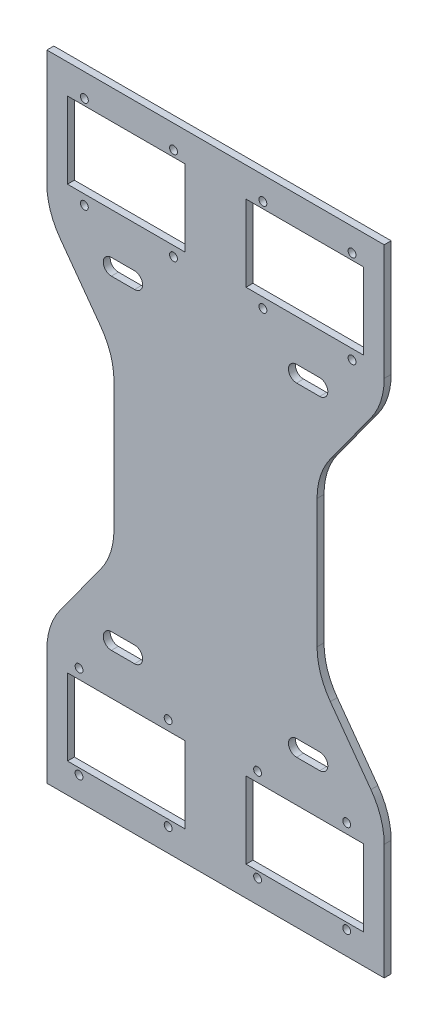
SolidWorks part; units mm, degrees
ref_plane "Alzado" through (0, 0, 0) normal (0, 0, 1) x (1, 0, 0)
ref_plane "Planta" through (0, 0, 0) normal (0, 1, 0) x (1, 0, 0)
ref_plane "Vista lateral" through (0, 0, 0) normal (1, 0, 0) x (0, 0, -1)
sketch "Croquis1" plane through (0, 0, 0) normal (0, 0, 1) x (1, 0, 0)
  line L1 (72.8628, -137.1535) -> (-72.8628, -137.1535)
  line L2 (72.8628, -137.1535) -> (72.8628, -77.4151)
  line L3 (72.8628, 137.1535) -> (-72.8628, 137.1535)
  line L4 (-72.8628, -137.1535) -> (-72.8628, -77.4151)
  line L5 (72.8628, -137.1535) -> (-72.8628, 137.1535) construction
  line L6 (72.8628, 137.1535) -> (-72.8628, -137.1535) construction
  line L7 (-72.8628, 0) -> (72.8628, 0) construction
  line L8 (0, -137.1535) -> (0, 137.1535) construction
  line L9 (-43.8628, -37.5) -> (-43.8628, 37.5)
  line L10 (-43.8628, 37.5) -> (-72.8628, 77.4151)
  line L11 (-43.8628, -37.5) -> (-72.8628, -77.4151)
  line L12 (43.8628, -37.5) -> (72.8628, -77.4151)
  line L13 (43.8628, -37.5) -> (43.8628, 37.5)
  line L14 (43.8628, 37.5) -> (72.8628, 77.4151)
  line L15 (-72.8628, 77.4151) -> (-72.8628, 137.1535)
  line L16 (72.8628, 77.4151) -> (72.8628, 137.1535)
  point P0 (0, 0)
  point P11 (0, 0)
  point P14 (-43.8628, 0)
  dimension "D1" = 145.7256
  dimension "D2" = 274.3069
  dimension "D3" = 144
  dimension "D4" = 144
  dimension "D5" = 29
  dimension "D6" = 75
  dimension "D7" = 137.1535
extrude "Saliente-Extruir1" add sketch "Croquis1" along normal blind 3
fillet "Redondeo1" radius 30 8 edges at (72.8628, 77.4151, 1.5) (43.8628, 37.5, 1.5) (43.8628, -37.5, 1.5) (72.8628, -77.4151, 1.5) (-43.8628, -37.5, 1.5) (-72.8628, -77.4151, 1.5) (-43.8628, 37.5, 1.5) (-72.8628, 77.4151, 1.5)
sketch "mid bores" plane through (0, 0, 0) normal (0, 0, 1) x (1, 0, 0)
  point P0 (-58, 71)
  point P1 (0, 110)
  point P2 (58, 71)
  point P4 (0, -110)
  point P5 (58, -71)
  point P6 (0, 0)
  point P7 (-58, -71)
  dimension "D1" = 71
  dimension "D2" = 110
  dimension "D3" = 58
  dimension "D6" = 110
  dimension "D4" = 2
  dimension "D5" = 2
sketch "Croquis2" plane through (0, 0, 3) normal (0, 0, 1) x (1, 0, 0)
  line L0 (-45, 70) -> (-35, 70) construction
  line L1 (-45, 73.5) -> (-35, 73.5)
  line L2 (-45, 66.5) -> (-35, 66.5)
  arc A0 (-45, 73.5) -> (-45, 66.5) centre (-45, 70) ccw
  arc A1 (-35, 66.5) -> (-35, 73.5) centre (-35, 70) ccw
  point P2 (-40, 70)
  point P10 (0, 0)
  dimension "D1" = 7
  dimension "D2" = 10
  dimension "D3" = 40
  dimension "D4" = 70
extrude "Cortar-Extruir1" cut sketch "Croquis2" against normal through all
mirror "Simetría1" about plane through (0, 0, 0) normal (0, 1, 0) of "Cortar-Extruir1"
mirror "Simetría2" about plane through (0, 0, 0) normal (1, 0, 0) of "Simetría1"
sketch "ibt2 bores" plane through (0, 0, 3) normal (0, 0, 1) x (1, 0, 0)
  point P0 (-18.1628, 127.1535)
  point P1 (-18.1628, 87.1535)
  point P2 (-56.6628, 87.1535)
  point P3 (20.4628, 127.1535)
  point P4 (-56.6628, 127.1535)
  point P5 (20.4628, 87.1535)
  point P6 (58.9628, 87.1535)
  point P7 (58.9628, 127.1535)
  point P8 (-20.4628, -87.1535)
  point P9 (-58.9628, -87.1535)
  point P10 (18.1628, -87.1535)
  point P11 (56.6628, -87.1535)
  point P12 (56.6628, -127.1535)
  point P13 (18.1628, -127.1535)
  point P14 (-20.4628, -127.1535)
  point P15 (-58.9628, -127.1535)
hole_wizard "Taladro de margen para M31" positions "Croquis13" profile "Croquis15" hole size "M3" standard "Ansi Metric" end condition through all
sketch "Croquis13" plane through (0, 0, 3) normal (0, 0, 1) x (1, 0, 0)
  point P0 (-56.6628, 127.1535)
  point P3 (-18.1628, 127.1535)
  point P6 (-18.1628, 87.1535)
  point P9 (-56.6628, 87.1535)
  point P14 (20.4628, 127.1535)
  point P17 (20.4628, 87.1535)
  point P20 (58.9628, 87.1535)
  point P23 (58.9628, 127.1535)
  point P27 (-58.9628, -87.1535)
  point P30 (-20.4628, -87.1535)
  point P33 (-20.4628, -127.1535)
  point P36 (-58.9628, -127.1535)
  point P39 (18.1628, -87.1535)
  point P42 (56.6628, -87.1535)
  point P45 (56.6628, -127.1535)
  point P48 (18.1628, -127.1535)
sketch "Croquis15" plane through (-56.6628, 127.1535, 3) normal (1, 0, 0) x (0, -1, 0)
  line L0 (0, 0) -> (0, 3)
  line L1 (0, 3) -> (1.7, 3)
  line L2 (1.7, 3) -> (1.7, 0)
  line L5 (1.7, 0) -> (0, 0)
  line L11 (0, -6.35) -> (0, 107.95) construction
  dimension "Diámetro de taladro hasta el siguiente" = 3.4
  dimension "Profundidad de taladro hasta el siguiente" = 3
sketch "Croquis16" plane through (0, 0, 0) normal (0, 0, -1) x (-1, 0, 0)
  line L0 (13.5628, 124.0035) -> (63.5628, 124.0035) construction
  line L1 (63.5628, 124.0035) -> (63.5628, 91.8035) construction
  line L2 (63.5628, 91.8035) -> (13.5628, 91.8035) construction
  line L3 (13.5628, 91.8035) -> (13.5628, 124.0035) construction
  line L4 (-13.5628, 124.0035) -> (-13.5628, 91.8035) construction
  line L5 (-13.5628, 91.8035) -> (-63.5628, 91.8035) construction
  line L6 (-63.5628, 91.8035) -> (-63.5628, 124.0035) construction
  line L7 (-63.5628, 124.0035) -> (-13.5628, 124.0035) construction
  line L8 (-63.9628, 124.4035) -> (-13.1628, 124.4035)
  line L9 (-13.1628, 124.4035) -> (-13.1628, 91.4035)
  line L10 (-13.1628, 91.4035) -> (-63.9628, 91.4035)
  line L11 (-63.9628, 91.4035) -> (-63.9628, 124.4035)
  line L12 (13.1628, 91.4035) -> (13.1628, 124.4035)
  line L13 (13.1628, 124.4035) -> (63.9628, 124.4035)
  line L14 (63.9628, 124.4035) -> (63.9628, 91.4035)
  line L15 (63.9628, 91.4035) -> (13.1628, 91.4035)
  line L16 (-63.5628, -91.8035) -> (-13.5628, -91.8035) construction
  line L17 (-13.5628, -91.8035) -> (-13.5628, -124.0035) construction
  line L18 (-13.5628, -124.0035) -> (-63.5628, -124.0035) construction
  line L19 (-63.5628, -124.0035) -> (-63.5628, -91.8035) construction
  line L20 (13.5628, -91.8035) -> (13.5628, -124.0035) construction
  line L21 (13.5628, -124.0035) -> (63.5628, -124.0035) construction
  line L22 (63.5628, -124.0035) -> (63.5628, -91.8035) construction
  line L23 (63.5628, -91.8035) -> (13.5628, -91.8035) construction
  line L24 (-63.9628, -91.4035) -> (-13.1628, -91.4035)
  line L25 (-13.1628, -91.4035) -> (-13.1628, -124.4035)
  line L26 (-13.1628, -124.4035) -> (-63.9628, -124.4035)
  line L27 (-63.9628, -124.4035) -> (-63.9628, -91.4035)
  line L28 (13.1628, -91.4035) -> (13.1628, -124.4035)
  line L29 (13.1628, -124.4035) -> (63.9628, -124.4035)
  line L30 (63.9628, -124.4035) -> (63.9628, -91.4035)
  line L31 (63.9628, -91.4035) -> (13.1628, -91.4035)
  dimension "D1" = 0.4
  dimension "D2" = 0.4
extrude "Cortar-Extruir2" cut sketch "Croquis16" against normal through all
